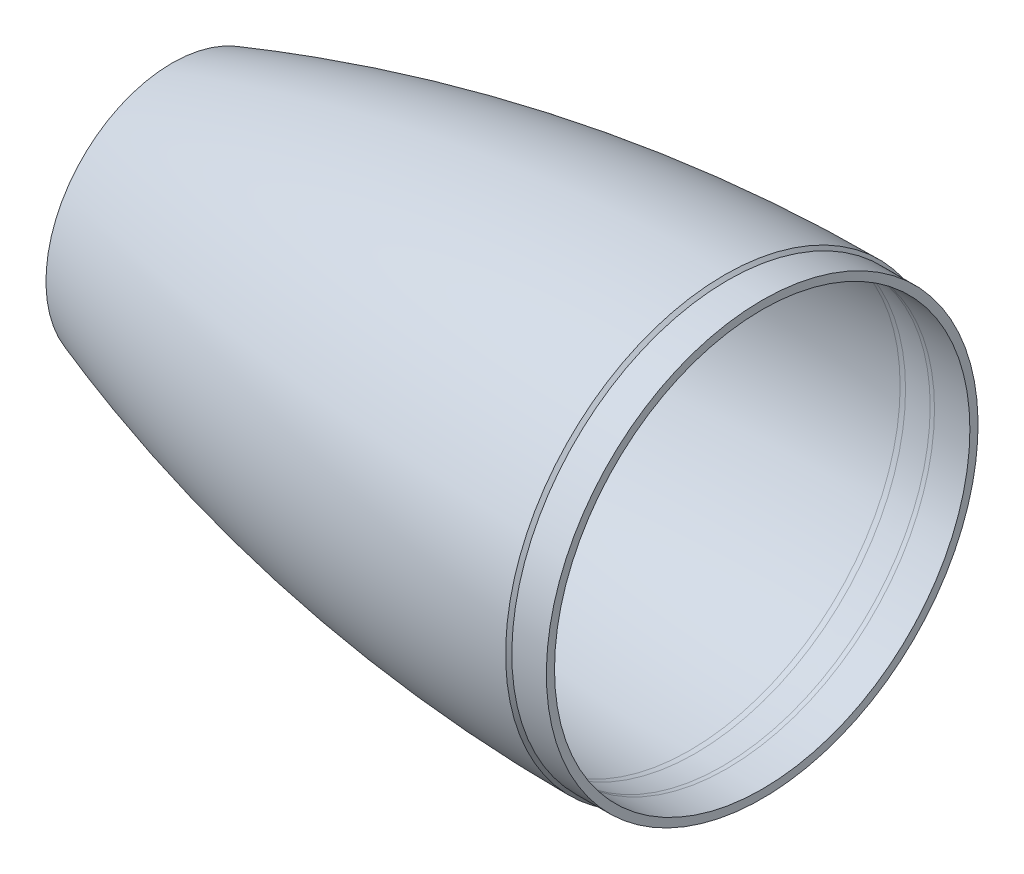
SolidWorks part; units mm, degrees
ref_plane "Front Plane" through (0, 0, 0) normal (0, 0, 1) x (1, 0, 0)
ref_plane "Top Plane" through (0, 0, 0) normal (0, 1, 0) x (1, 0, 0)
ref_plane "Right Plane" through (0, 0, 0) normal (1, 0, 0) x (0, 0, -1)
sketch "Sketch1" plane through (0, 0, 0) normal (0, 0, 1) x (1, 0, 0)
  line L4 (0, 0) -> (-304.8, 0) construction
  line L9 (0, 76.3778) -> (0, 0) construction
  line L10 (0, 80.518) -> (50.8, 80.518) construction
  line L11 (-203.2, 46.355) -> (-203.2, 41.4655)
  line L12 (-203.2, 41.4655) -> (-181.891, 41.4655)
  line L13 (-174.0697, 43.1452) -> (-128.9003, 63.4837)
  line L15 (1.143, 79.375) -> (13.843, 79.375)
  line L16 (0, 80.518) -> (1.143, 79.375)
  line L17 (0.8317, 76.3778) -> (13.843, 76.3778)
  line L18 (13.843, 76.3778) -> (13.843, 79.375)
  line L19 (-0.8286, 76.4503) -> (-10.7639, 77.3195)
  arc A4 (0, 80.518) -> (-203.2, 46.355) centre (0, -540.8758) ccw
  arc A5 (-12.8191, 77.3879) -> (-124.9274, 64.7705) centre (0, -540.8758) ccw
  arc A6 (0, 77.5208) -> (-202.2199, 43.5226) centre (0, -540.8758) ccw construction
  arc A7 (-174.0697, 43.1452) -> (-181.891, 41.4655) centre (-181.891, 60.5155) cw
  arc A8 (-128.9003, 63.4837) -> (-124.9274, 64.7705) centre (-121.079, 46.1133) cw
  arc A9 (-10.7639, 77.3195) -> (-12.8191, 77.3879) centre (-12.4242, 58.342) ccw
  arc A10 (-0.8286, 76.4503) -> (0.8317, 76.3778) centre (0.8317, 95.4278) ccw
  point P6 (0, 0)
  point P8 (-57.2734, -19.8104)
  point P9 (0, 313.4439)
  point P10 (-150.9565, 274.6984)
  point P21 (-177.8, 41.4655)
  point P24 (-127, 64.3393)
  point P28 (1.1612, 79.375)
  dimension "D7" = 25.4
  dimension "D10" = 19.05
  dimension "D11" = 19.05
  dimension "D17" = 19.05
  dimension "D1" = 161.036
  dimension "D2" = 50.8
  dimension "D3" = 203.2
  dimension "D4" = 92.71
  dimension "D6" = 82.931
  dimension "D8" = 50.8
  dimension "D9" = 304.8
  dimension "D12" = 12.7
  dimension "D13" = 158.75
  dimension "D14" = 45
  dimension "D15" = 2.9972
  dimension "D16" = 175
  dimension "D5" = 2.9972
revolve "Revolve1" add sketch "Sketch1" angle 360 about L4
